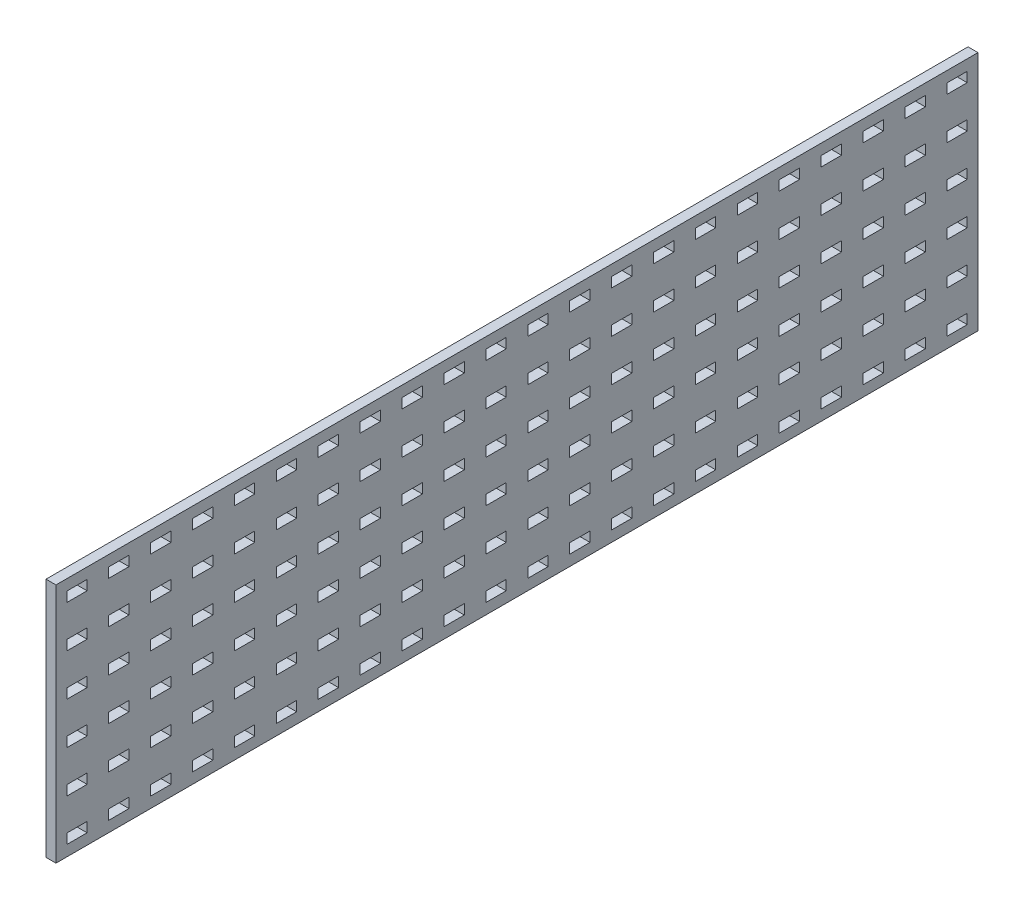
SolidWorks part; units mm, degrees
ref_plane "Front Plane" through (0, 0, 0) normal (0, 0, 1) x (1, 0, 0)
ref_plane "Top Plane" through (0, 0, 0) normal (0, 1, 0) x (1, 0, 0)
ref_plane "Right Plane" through (0, 0, 0) normal (1, 0, 0) x (0, 0, -1)
sketch "Sketch1" plane through (0, 0, 0) normal (1, 0, 0) x (0, 0, -1)
  line L1 (-279.4, -73.025) -> (279.4, -73.025)
  line L2 (-279.4, -73.025) -> (-279.4, 73.025)
  line L3 (-279.4, 73.025) -> (279.4, 73.025)
  line L4 (279.4, -73.025) -> (279.4, 73.025)
  line L5 (-279.4, -73.025) -> (279.4, 73.025) construction
  line L6 (-279.4, 73.025) -> (279.4, -73.025) construction
  point P0 (0, 0)
  dimension "D1" = 558.8
  dimension "D2" = 146.05
extrude "Boss-Extrude1" add sketch "Sketch1" along normal mid plane 6.0452
sketch "Sketch2" plane through (3.0226, 0, 0) normal (1, 0, 0) x (0, 0, -1)
  line L0 (-279.4, -73.025) -> (279.4, -73.025) construction
  line L1 (260.5405, -60.5) -> (272.8595, -60.5)
  line L2 (260.5405, -60.5) -> (260.5405, -66.5)
  line L3 (260.5405, -66.5) -> (272.8595, -66.5)
  line L4 (272.8595, -60.5) -> (272.8595, -66.5)
  line L5 (260.5405, -60.5) -> (272.8595, -66.5) construction
  line L6 (260.5405, -66.5) -> (272.8595, -60.5) construction
  line L7 (279.4, -73.025) -> (279.4, 73.025) construction
  line L8 (235.1405, -66.5) -> (247.4595, -66.5)
  line L9 (235.1405, -60.5) -> (235.1405, -66.5)
  line L10 (235.1405, -60.5) -> (247.4595, -60.5)
  line L11 (247.4595, -60.5) -> (247.4595, -66.5)
  line L12 (209.7405, -66.5) -> (222.0595, -66.5)
  line L13 (209.7405, -60.5) -> (209.7405, -66.5)
  line L14 (209.7405, -60.5) -> (222.0595, -60.5)
  line L15 (222.0595, -60.5) -> (222.0595, -66.5)
  line L16 (184.3405, -66.5) -> (196.6595, -66.5)
  line L17 (184.3405, -60.5) -> (184.3405, -66.5)
  line L18 (184.3405, -60.5) -> (196.6595, -60.5)
  line L19 (196.6595, -60.5) -> (196.6595, -66.5)
  line L20 (158.9405, -66.5) -> (171.2595, -66.5)
  line L21 (158.9405, -60.5) -> (158.9405, -66.5)
  line L22 (158.9405, -60.5) -> (171.2595, -60.5)
  line L23 (171.2595, -60.5) -> (171.2595, -66.5)
  line L24 (133.5405, -66.5) -> (145.8595, -66.5)
  line L25 (133.5405, -60.5) -> (133.5405, -66.5)
  line L26 (133.5405, -60.5) -> (145.8595, -60.5)
  line L27 (145.8595, -60.5) -> (145.8595, -66.5)
  line L28 (108.1405, -66.5) -> (120.4595, -66.5)
  line L29 (108.1405, -60.5) -> (108.1405, -66.5)
  line L30 (108.1405, -60.5) -> (120.4595, -60.5)
  line L31 (120.4595, -60.5) -> (120.4595, -66.5)
  line L32 (82.7405, -66.5) -> (95.0595, -66.5)
  line L33 (82.7405, -60.5) -> (82.7405, -66.5)
  line L34 (82.7405, -60.5) -> (95.0595, -60.5)
  line L35 (95.0595, -60.5) -> (95.0595, -66.5)
  line L36 (57.3405, -66.5) -> (69.6595, -66.5)
  line L37 (57.3405, -60.5) -> (57.3405, -66.5)
  line L38 (57.3405, -60.5) -> (69.6595, -60.5)
  line L39 (69.6595, -60.5) -> (69.6595, -66.5)
  line L40 (31.9405, -66.5) -> (44.2595, -66.5)
  line L41 (31.9405, -60.5) -> (31.9405, -66.5)
  line L42 (31.9405, -60.5) -> (44.2595, -60.5)
  line L43 (44.2595, -60.5) -> (44.2595, -66.5)
  line L44 (6.5405, -66.5) -> (18.8595, -66.5)
  line L45 (6.5405, -60.5) -> (6.5405, -66.5)
  line L46 (6.5405, -60.5) -> (18.8595, -60.5)
  line L47 (18.8595, -60.5) -> (18.8595, -66.5)
  line L48 (-18.8595, -66.5) -> (-6.5405, -66.5)
  line L49 (-18.8595, -60.5) -> (-18.8595, -66.5)
  line L50 (-18.8595, -60.5) -> (-6.5405, -60.5)
  line L51 (-6.5405, -60.5) -> (-6.5405, -66.5)
  line L52 (-44.2595, -66.5) -> (-31.9405, -66.5)
  line L53 (-44.2595, -60.5) -> (-44.2595, -66.5)
  line L54 (-44.2595, -60.5) -> (-31.9405, -60.5)
  line L55 (-31.9405, -60.5) -> (-31.9405, -66.5)
  line L56 (-69.6595, -66.5) -> (-57.3405, -66.5)
  line L57 (-69.6595, -60.5) -> (-69.6595, -66.5)
  line L58 (-69.6595, -60.5) -> (-57.3405, -60.5)
  line L59 (-57.3405, -60.5) -> (-57.3405, -66.5)
  line L60 (-95.0595, -66.5) -> (-82.7405, -66.5)
  line L61 (-95.0595, -60.5) -> (-95.0595, -66.5)
  line L62 (-95.0595, -60.5) -> (-82.7405, -60.5)
  line L63 (-82.7405, -60.5) -> (-82.7405, -66.5)
  line L64 (-120.4595, -66.5) -> (-108.1405, -66.5)
  line L65 (-120.4595, -60.5) -> (-120.4595, -66.5)
  line L66 (-120.4595, -60.5) -> (-108.1405, -60.5)
  line L67 (-108.1405, -60.5) -> (-108.1405, -66.5)
  line L68 (-145.8595, -66.5) -> (-133.5405, -66.5)
  line L69 (-145.8595, -60.5) -> (-145.8595, -66.5)
  line L70 (-145.8595, -60.5) -> (-133.5405, -60.5)
  line L71 (-133.5405, -60.5) -> (-133.5405, -66.5)
  line L72 (-171.2595, -66.5) -> (-158.9405, -66.5)
  line L73 (-171.2595, -60.5) -> (-171.2595, -66.5)
  line L74 (-171.2595, -60.5) -> (-158.9405, -60.5)
  line L75 (-158.9405, -60.5) -> (-158.9405, -66.5)
  line L76 (-196.6595, -66.5) -> (-184.3405, -66.5)
  line L77 (-196.6595, -60.5) -> (-196.6595, -66.5)
  line L78 (-196.6595, -60.5) -> (-184.3405, -60.5)
  line L79 (-184.3405, -60.5) -> (-184.3405, -66.5)
  line L80 (-222.0595, -66.5) -> (-209.7405, -66.5)
  line L81 (-222.0595, -60.5) -> (-222.0595, -66.5)
  line L82 (-222.0595, -60.5) -> (-209.7405, -60.5)
  line L83 (-209.7405, -60.5) -> (-209.7405, -66.5)
  line L84 (-247.4595, -66.5) -> (-235.1405, -66.5)
  line L85 (-247.4595, -60.5) -> (-247.4595, -66.5)
  line L86 (-247.4595, -60.5) -> (-235.1405, -60.5)
  line L87 (-235.1405, -60.5) -> (-235.1405, -66.5)
  line L88 (-272.8595, -66.5) -> (-260.5405, -66.5)
  line L89 (-272.8595, -60.5) -> (-272.8595, -66.5)
  line L90 (-272.8595, -60.5) -> (-260.5405, -60.5)
  line L91 (-260.5405, -60.5) -> (-260.5405, -66.5)
  line L92 (235.1405, -41.1) -> (247.4595, -41.1)
  line L93 (235.1405, -35.1) -> (235.1405, -41.1)
  line L94 (235.1405, -35.1) -> (247.4595, -35.1)
  line L95 (247.4595, -35.1) -> (247.4595, -41.1)
  line L96 (209.7405, -41.1) -> (222.0595, -41.1)
  line L97 (209.7405, -35.1) -> (209.7405, -41.1)
  line L98 (209.7405, -35.1) -> (222.0595, -35.1)
  line L99 (222.0595, -35.1) -> (222.0595, -41.1)
  line L100 (184.3405, -41.1) -> (196.6595, -41.1)
  line L101 (184.3405, -35.1) -> (184.3405, -41.1)
  line L102 (184.3405, -35.1) -> (196.6595, -35.1)
  line L103 (196.6595, -35.1) -> (196.6595, -41.1)
  line L104 (158.9405, -41.1) -> (171.2595, -41.1)
  line L105 (158.9405, -35.1) -> (158.9405, -41.1)
  line L106 (158.9405, -35.1) -> (171.2595, -35.1)
  line L107 (171.2595, -35.1) -> (171.2595, -41.1)
  line L108 (133.5405, -41.1) -> (145.8595, -41.1)
  line L109 (133.5405, -35.1) -> (133.5405, -41.1)
  line L110 (133.5405, -35.1) -> (145.8595, -35.1)
  line L111 (145.8595, -35.1) -> (145.8595, -41.1)
  line L112 (108.1405, -41.1) -> (120.4595, -41.1)
  line L113 (108.1405, -35.1) -> (108.1405, -41.1)
  line L114 (108.1405, -35.1) -> (120.4595, -35.1)
  line L115 (120.4595, -35.1) -> (120.4595, -41.1)
  line L116 (82.7405, -41.1) -> (95.0595, -41.1)
  line L117 (82.7405, -35.1) -> (82.7405, -41.1)
  line L118 (82.7405, -35.1) -> (95.0595, -35.1)
  line L119 (95.0595, -35.1) -> (95.0595, -41.1)
  line L120 (57.3405, -41.1) -> (69.6595, -41.1)
  line L121 (57.3405, -35.1) -> (57.3405, -41.1)
  line L122 (57.3405, -35.1) -> (69.6595, -35.1)
  line L123 (69.6595, -35.1) -> (69.6595, -41.1)
  line L124 (31.9405, -41.1) -> (44.2595, -41.1)
  line L125 (31.9405, -35.1) -> (31.9405, -41.1)
  line L126 (31.9405, -35.1) -> (44.2595, -35.1)
  line L127 (44.2595, -35.1) -> (44.2595, -41.1)
  line L128 (6.5405, -41.1) -> (18.8595, -41.1)
  line L129 (6.5405, -35.1) -> (6.5405, -41.1)
  line L130 (6.5405, -35.1) -> (18.8595, -35.1)
  line L131 (18.8595, -35.1) -> (18.8595, -41.1)
  line L132 (-18.8595, -41.1) -> (-6.5405, -41.1)
  line L133 (-18.8595, -35.1) -> (-18.8595, -41.1)
  line L134 (-18.8595, -35.1) -> (-6.5405, -35.1)
  line L135 (-6.5405, -35.1) -> (-6.5405, -41.1)
  line L136 (-44.2595, -41.1) -> (-31.9405, -41.1)
  line L137 (-44.2595, -35.1) -> (-44.2595, -41.1)
  line L138 (-44.2595, -35.1) -> (-31.9405, -35.1)
  line L139 (-31.9405, -35.1) -> (-31.9405, -41.1)
  line L140 (-69.6595, -41.1) -> (-57.3405, -41.1)
  line L141 (-69.6595, -35.1) -> (-69.6595, -41.1)
  line L142 (-69.6595, -35.1) -> (-57.3405, -35.1)
  line L143 (-57.3405, -35.1) -> (-57.3405, -41.1)
  line L144 (-95.0595, -41.1) -> (-82.7405, -41.1)
  line L145 (-95.0595, -35.1) -> (-95.0595, -41.1)
  line L146 (-95.0595, -35.1) -> (-82.7405, -35.1)
  line L147 (-82.7405, -35.1) -> (-82.7405, -41.1)
  line L148 (-120.4595, -41.1) -> (-108.1405, -41.1)
  line L149 (-120.4595, -35.1) -> (-120.4595, -41.1)
  line L150 (-120.4595, -35.1) -> (-108.1405, -35.1)
  line L151 (-108.1405, -35.1) -> (-108.1405, -41.1)
  line L152 (-145.8595, -41.1) -> (-133.5405, -41.1)
  line L153 (-145.8595, -35.1) -> (-145.8595, -41.1)
  line L154 (-145.8595, -35.1) -> (-133.5405, -35.1)
  line L155 (-133.5405, -35.1) -> (-133.5405, -41.1)
  line L156 (-171.2595, -41.1) -> (-158.9405, -41.1)
  line L157 (-171.2595, -35.1) -> (-171.2595, -41.1)
  line L158 (-171.2595, -35.1) -> (-158.9405, -35.1)
  line L159 (-158.9405, -35.1) -> (-158.9405, -41.1)
  line L160 (-196.6595, -41.1) -> (-184.3405, -41.1)
  line L161 (-196.6595, -35.1) -> (-196.6595, -41.1)
  line L162 (-196.6595, -35.1) -> (-184.3405, -35.1)
  line L163 (-184.3405, -35.1) -> (-184.3405, -41.1)
  line L164 (-222.0595, -41.1) -> (-209.7405, -41.1)
  line L165 (-222.0595, -35.1) -> (-222.0595, -41.1)
  line L166 (-222.0595, -35.1) -> (-209.7405, -35.1)
  line L167 (-209.7405, -35.1) -> (-209.7405, -41.1)
  line L168 (-247.4595, -41.1) -> (-235.1405, -41.1)
  line L169 (-247.4595, -35.1) -> (-247.4595, -41.1)
  line L170 (-247.4595, -35.1) -> (-235.1405, -35.1)
  line L171 (-235.1405, -35.1) -> (-235.1405, -41.1)
  line L172 (-272.8595, -41.1) -> (-260.5405, -41.1)
  line L173 (-272.8595, -35.1) -> (-272.8595, -41.1)
  line L174 (-272.8595, -35.1) -> (-260.5405, -35.1)
  line L175 (-260.5405, -35.1) -> (-260.5405, -41.1)
  line L176 (235.1405, -15.7) -> (247.4595, -15.7)
  line L177 (235.1405, -9.7) -> (235.1405, -15.7)
  line L178 (235.1405, -9.7) -> (247.4595, -9.7)
  line L179 (247.4595, -9.7) -> (247.4595, -15.7)
  line L180 (209.7405, -15.7) -> (222.0595, -15.7)
  line L181 (209.7405, -9.7) -> (209.7405, -15.7)
  line L182 (209.7405, -9.7) -> (222.0595, -9.7)
  line L183 (222.0595, -9.7) -> (222.0595, -15.7)
  line L184 (184.3405, -15.7) -> (196.6595, -15.7)
  line L185 (184.3405, -9.7) -> (184.3405, -15.7)
  line L186 (184.3405, -9.7) -> (196.6595, -9.7)
  line L187 (196.6595, -9.7) -> (196.6595, -15.7)
  line L188 (158.9405, -15.7) -> (171.2595, -15.7)
  line L189 (158.9405, -9.7) -> (158.9405, -15.7)
  line L190 (158.9405, -9.7) -> (171.2595, -9.7)
  line L191 (171.2595, -9.7) -> (171.2595, -15.7)
  line L192 (133.5405, -15.7) -> (145.8595, -15.7)
  line L193 (133.5405, -9.7) -> (133.5405, -15.7)
  line L194 (133.5405, -9.7) -> (145.8595, -9.7)
  line L195 (145.8595, -9.7) -> (145.8595, -15.7)
  line L196 (108.1405, -15.7) -> (120.4595, -15.7)
  line L197 (108.1405, -9.7) -> (108.1405, -15.7)
  line L198 (108.1405, -9.7) -> (120.4595, -9.7)
  line L199 (120.4595, -9.7) -> (120.4595, -15.7)
  line L200 (82.7405, -15.7) -> (95.0595, -15.7)
  line L201 (82.7405, -9.7) -> (82.7405, -15.7)
  line L202 (82.7405, -9.7) -> (95.0595, -9.7)
  line L203 (95.0595, -9.7) -> (95.0595, -15.7)
  line L204 (57.3405, -15.7) -> (69.6595, -15.7)
  line L205 (57.3405, -9.7) -> (57.3405, -15.7)
  line L206 (57.3405, -9.7) -> (69.6595, -9.7)
  line L207 (69.6595, -9.7) -> (69.6595, -15.7)
  line L208 (31.9405, -15.7) -> (44.2595, -15.7)
  line L209 (31.9405, -9.7) -> (31.9405, -15.7)
  line L210 (31.9405, -9.7) -> (44.2595, -9.7)
  line L211 (44.2595, -9.7) -> (44.2595, -15.7)
  line L212 (6.5405, -15.7) -> (18.8595, -15.7)
  line L213 (6.5405, -9.7) -> (6.5405, -15.7)
  line L214 (6.5405, -9.7) -> (18.8595, -9.7)
  line L215 (18.8595, -9.7) -> (18.8595, -15.7)
  line L216 (-18.8595, -15.7) -> (-6.5405, -15.7)
  line L217 (-18.8595, -9.7) -> (-18.8595, -15.7)
  line L218 (-18.8595, -9.7) -> (-6.5405, -9.7)
  line L219 (-6.5405, -9.7) -> (-6.5405, -15.7)
  line L220 (-44.2595, -15.7) -> (-31.9405, -15.7)
  line L221 (-44.2595, -9.7) -> (-44.2595, -15.7)
  line L222 (-44.2595, -9.7) -> (-31.9405, -9.7)
  line L223 (-31.9405, -9.7) -> (-31.9405, -15.7)
  line L224 (-69.6595, -15.7) -> (-57.3405, -15.7)
  line L225 (-69.6595, -9.7) -> (-69.6595, -15.7)
  line L226 (-69.6595, -9.7) -> (-57.3405, -9.7)
  line L227 (-57.3405, -9.7) -> (-57.3405, -15.7)
  line L228 (-95.0595, -15.7) -> (-82.7405, -15.7)
  line L229 (-95.0595, -9.7) -> (-95.0595, -15.7)
  line L230 (-95.0595, -9.7) -> (-82.7405, -9.7)
  line L231 (-82.7405, -9.7) -> (-82.7405, -15.7)
  line L232 (-120.4595, -15.7) -> (-108.1405, -15.7)
  line L233 (-120.4595, -9.7) -> (-120.4595, -15.7)
  line L234 (-120.4595, -9.7) -> (-108.1405, -9.7)
  line L235 (-108.1405, -9.7) -> (-108.1405, -15.7)
  line L236 (-145.8595, -15.7) -> (-133.5405, -15.7)
  line L237 (-145.8595, -9.7) -> (-145.8595, -15.7)
  line L238 (-145.8595, -9.7) -> (-133.5405, -9.7)
  line L239 (-133.5405, -9.7) -> (-133.5405, -15.7)
  line L240 (-171.2595, -15.7) -> (-158.9405, -15.7)
  line L241 (-171.2595, -9.7) -> (-171.2595, -15.7)
  line L242 (-171.2595, -9.7) -> (-158.9405, -9.7)
  line L243 (-158.9405, -9.7) -> (-158.9405, -15.7)
  line L244 (-196.6595, -15.7) -> (-184.3405, -15.7)
  line L245 (-196.6595, -9.7) -> (-196.6595, -15.7)
  line L246 (-196.6595, -9.7) -> (-184.3405, -9.7)
  line L247 (-184.3405, -9.7) -> (-184.3405, -15.7)
  line L248 (-222.0595, -15.7) -> (-209.7405, -15.7)
  line L249 (-222.0595, -9.7) -> (-222.0595, -15.7)
  line L250 (-222.0595, -9.7) -> (-209.7405, -9.7)
  line L251 (-209.7405, -9.7) -> (-209.7405, -15.7)
  line L252 (-247.4595, -15.7) -> (-235.1405, -15.7)
  line L253 (-247.4595, -9.7) -> (-247.4595, -15.7)
  line L254 (-247.4595, -9.7) -> (-235.1405, -9.7)
  line L255 (-235.1405, -9.7) -> (-235.1405, -15.7)
  line L256 (-272.8595, -15.7) -> (-260.5405, -15.7)
  line L257 (-272.8595, -9.7) -> (-272.8595, -15.7)
  line L258 (-272.8595, -9.7) -> (-260.5405, -9.7)
  line L259 (-260.5405, -9.7) -> (-260.5405, -15.7)
  line L260 (235.1405, 9.7) -> (247.4595, 9.7)
  line L261 (235.1405, 15.7) -> (235.1405, 9.7)
  line L262 (235.1405, 15.7) -> (247.4595, 15.7)
  line L263 (247.4595, 15.7) -> (247.4595, 9.7)
  line L264 (209.7405, 9.7) -> (222.0595, 9.7)
  line L265 (209.7405, 15.7) -> (209.7405, 9.7)
  line L266 (209.7405, 15.7) -> (222.0595, 15.7)
  line L267 (222.0595, 15.7) -> (222.0595, 9.7)
  line L268 (184.3405, 9.7) -> (196.6595, 9.7)
  line L269 (184.3405, 15.7) -> (184.3405, 9.7)
  line L270 (184.3405, 15.7) -> (196.6595, 15.7)
  line L271 (196.6595, 15.7) -> (196.6595, 9.7)
  line L272 (158.9405, 9.7) -> (171.2595, 9.7)
  line L273 (158.9405, 15.7) -> (158.9405, 9.7)
  line L274 (158.9405, 15.7) -> (171.2595, 15.7)
  line L275 (171.2595, 15.7) -> (171.2595, 9.7)
  line L276 (133.5405, 9.7) -> (145.8595, 9.7)
  line L277 (133.5405, 15.7) -> (133.5405, 9.7)
  line L278 (133.5405, 15.7) -> (145.8595, 15.7)
  line L279 (145.8595, 15.7) -> (145.8595, 9.7)
  line L280 (108.1405, 9.7) -> (120.4595, 9.7)
  line L281 (108.1405, 15.7) -> (108.1405, 9.7)
  line L282 (108.1405, 15.7) -> (120.4595, 15.7)
  line L283 (120.4595, 15.7) -> (120.4595, 9.7)
  line L284 (82.7405, 9.7) -> (95.0595, 9.7)
  line L285 (82.7405, 15.7) -> (82.7405, 9.7)
  line L286 (82.7405, 15.7) -> (95.0595, 15.7)
  line L287 (95.0595, 15.7) -> (95.0595, 9.7)
  line L288 (57.3405, 9.7) -> (69.6595, 9.7)
  line L289 (57.3405, 15.7) -> (57.3405, 9.7)
  line L290 (57.3405, 15.7) -> (69.6595, 15.7)
  line L291 (69.6595, 15.7) -> (69.6595, 9.7)
  line L292 (31.9405, 9.7) -> (44.2595, 9.7)
  line L293 (31.9405, 15.7) -> (31.9405, 9.7)
  line L294 (31.9405, 15.7) -> (44.2595, 15.7)
  line L295 (44.2595, 15.7) -> (44.2595, 9.7)
  line L296 (6.5405, 9.7) -> (18.8595, 9.7)
  line L297 (6.5405, 15.7) -> (6.5405, 9.7)
  line L298 (6.5405, 15.7) -> (18.8595, 15.7)
  line L299 (18.8595, 15.7) -> (18.8595, 9.7)
  line L300 (-18.8595, 9.7) -> (-6.5405, 9.7)
  line L301 (-18.8595, 15.7) -> (-18.8595, 9.7)
  line L302 (-18.8595, 15.7) -> (-6.5405, 15.7)
  line L303 (-6.5405, 15.7) -> (-6.5405, 9.7)
  line L304 (-44.2595, 9.7) -> (-31.9405, 9.7)
  line L305 (-44.2595, 15.7) -> (-44.2595, 9.7)
  line L306 (-44.2595, 15.7) -> (-31.9405, 15.7)
  line L307 (-31.9405, 15.7) -> (-31.9405, 9.7)
  line L308 (-69.6595, 9.7) -> (-57.3405, 9.7)
  line L309 (-69.6595, 15.7) -> (-69.6595, 9.7)
  line L310 (-69.6595, 15.7) -> (-57.3405, 15.7)
  line L311 (-57.3405, 15.7) -> (-57.3405, 9.7)
  line L312 (-95.0595, 9.7) -> (-82.7405, 9.7)
  line L313 (-95.0595, 15.7) -> (-95.0595, 9.7)
  line L314 (-95.0595, 15.7) -> (-82.7405, 15.7)
  line L315 (-82.7405, 15.7) -> (-82.7405, 9.7)
  line L316 (-120.4595, 9.7) -> (-108.1405, 9.7)
  line L317 (-120.4595, 15.7) -> (-120.4595, 9.7)
  line L318 (-120.4595, 15.7) -> (-108.1405, 15.7)
  line L319 (-108.1405, 15.7) -> (-108.1405, 9.7)
  line L320 (-145.8595, 9.7) -> (-133.5405, 9.7)
  line L321 (-145.8595, 15.7) -> (-145.8595, 9.7)
  line L322 (-145.8595, 15.7) -> (-133.5405, 15.7)
  line L323 (-133.5405, 15.7) -> (-133.5405, 9.7)
  line L324 (-171.2595, 9.7) -> (-158.9405, 9.7)
  line L325 (-171.2595, 15.7) -> (-171.2595, 9.7)
  line L326 (-171.2595, 15.7) -> (-158.9405, 15.7)
  line L327 (-158.9405, 15.7) -> (-158.9405, 9.7)
  line L328 (-196.6595, 9.7) -> (-184.3405, 9.7)
  line L329 (-196.6595, 15.7) -> (-196.6595, 9.7)
  line L330 (-196.6595, 15.7) -> (-184.3405, 15.7)
  line L331 (-184.3405, 15.7) -> (-184.3405, 9.7)
  line L332 (-222.0595, 9.7) -> (-209.7405, 9.7)
  line L333 (-222.0595, 15.7) -> (-222.0595, 9.7)
  line L334 (-222.0595, 15.7) -> (-209.7405, 15.7)
  line L335 (-209.7405, 15.7) -> (-209.7405, 9.7)
  line L336 (-247.4595, 9.7) -> (-235.1405, 9.7)
  line L337 (-247.4595, 15.7) -> (-247.4595, 9.7)
  line L338 (-247.4595, 15.7) -> (-235.1405, 15.7)
  line L339 (-235.1405, 15.7) -> (-235.1405, 9.7)
  line L340 (-272.8595, 9.7) -> (-260.5405, 9.7)
  line L341 (-272.8595, 15.7) -> (-272.8595, 9.7)
  line L342 (-272.8595, 15.7) -> (-260.5405, 15.7)
  line L343 (-260.5405, 15.7) -> (-260.5405, 9.7)
  line L344 (235.1405, 35.1) -> (247.4595, 35.1)
  line L345 (235.1405, 41.1) -> (235.1405, 35.1)
  line L346 (235.1405, 41.1) -> (247.4595, 41.1)
  line L347 (247.4595, 41.1) -> (247.4595, 35.1)
  line L348 (209.7405, 35.1) -> (222.0595, 35.1)
  line L349 (209.7405, 41.1) -> (209.7405, 35.1)
  line L350 (209.7405, 41.1) -> (222.0595, 41.1)
  line L351 (222.0595, 41.1) -> (222.0595, 35.1)
  line L352 (184.3405, 35.1) -> (196.6595, 35.1)
  line L353 (184.3405, 41.1) -> (184.3405, 35.1)
  line L354 (184.3405, 41.1) -> (196.6595, 41.1)
  line L355 (196.6595, 41.1) -> (196.6595, 35.1)
  line L356 (158.9405, 35.1) -> (171.2595, 35.1)
  line L357 (158.9405, 41.1) -> (158.9405, 35.1)
  line L358 (158.9405, 41.1) -> (171.2595, 41.1)
  line L359 (171.2595, 41.1) -> (171.2595, 35.1)
  line L360 (133.5405, 35.1) -> (145.8595, 35.1)
  line L361 (133.5405, 41.1) -> (133.5405, 35.1)
  line L362 (133.5405, 41.1) -> (145.8595, 41.1)
  line L363 (145.8595, 41.1) -> (145.8595, 35.1)
  line L364 (108.1405, 35.1) -> (120.4595, 35.1)
  line L365 (108.1405, 41.1) -> (108.1405, 35.1)
  line L366 (108.1405, 41.1) -> (120.4595, 41.1)
  line L367 (120.4595, 41.1) -> (120.4595, 35.1)
  line L368 (82.7405, 35.1) -> (95.0595, 35.1)
  line L369 (82.7405, 41.1) -> (82.7405, 35.1)
  line L370 (82.7405, 41.1) -> (95.0595, 41.1)
  line L371 (95.0595, 41.1) -> (95.0595, 35.1)
  line L372 (57.3405, 35.1) -> (69.6595, 35.1)
  line L373 (57.3405, 41.1) -> (57.3405, 35.1)
  line L374 (57.3405, 41.1) -> (69.6595, 41.1)
  line L375 (69.6595, 41.1) -> (69.6595, 35.1)
  line L376 (31.9405, 35.1) -> (44.2595, 35.1)
  line L377 (31.9405, 41.1) -> (31.9405, 35.1)
  line L378 (31.9405, 41.1) -> (44.2595, 41.1)
  line L379 (44.2595, 41.1) -> (44.2595, 35.1)
  line L380 (6.5405, 35.1) -> (18.8595, 35.1)
  line L381 (6.5405, 41.1) -> (6.5405, 35.1)
  line L382 (6.5405, 41.1) -> (18.8595, 41.1)
  line L383 (18.8595, 41.1) -> (18.8595, 35.1)
  line L384 (-18.8595, 35.1) -> (-6.5405, 35.1)
  line L385 (-18.8595, 41.1) -> (-18.8595, 35.1)
  line L386 (-18.8595, 41.1) -> (-6.5405, 41.1)
  line L387 (-6.5405, 41.1) -> (-6.5405, 35.1)
  line L388 (-44.2595, 35.1) -> (-31.9405, 35.1)
  line L389 (-44.2595, 41.1) -> (-44.2595, 35.1)
  line L390 (-44.2595, 41.1) -> (-31.9405, 41.1)
  line L391 (-31.9405, 41.1) -> (-31.9405, 35.1)
  line L392 (-69.6595, 35.1) -> (-57.3405, 35.1)
  line L393 (-69.6595, 41.1) -> (-69.6595, 35.1)
  line L394 (-69.6595, 41.1) -> (-57.3405, 41.1)
  line L395 (-57.3405, 41.1) -> (-57.3405, 35.1)
  line L396 (-95.0595, 35.1) -> (-82.7405, 35.1)
  line L397 (-95.0595, 41.1) -> (-95.0595, 35.1)
  line L398 (-95.0595, 41.1) -> (-82.7405, 41.1)
  line L399 (-82.7405, 41.1) -> (-82.7405, 35.1)
  line L400 (-120.4595, 35.1) -> (-108.1405, 35.1)
  line L401 (-120.4595, 41.1) -> (-120.4595, 35.1)
  line L402 (-120.4595, 41.1) -> (-108.1405, 41.1)
  line L403 (-108.1405, 41.1) -> (-108.1405, 35.1)
  line L404 (-145.8595, 35.1) -> (-133.5405, 35.1)
  line L405 (-145.8595, 41.1) -> (-145.8595, 35.1)
  line L406 (-145.8595, 41.1) -> (-133.5405, 41.1)
  line L407 (-133.5405, 41.1) -> (-133.5405, 35.1)
  line L408 (-171.2595, 35.1) -> (-158.9405, 35.1)
  line L409 (-171.2595, 41.1) -> (-171.2595, 35.1)
  line L410 (-171.2595, 41.1) -> (-158.9405, 41.1)
  line L411 (-158.9405, 41.1) -> (-158.9405, 35.1)
  line L412 (-196.6595, 35.1) -> (-184.3405, 35.1)
  line L413 (-196.6595, 41.1) -> (-196.6595, 35.1)
  line L414 (-196.6595, 41.1) -> (-184.3405, 41.1)
  line L415 (-184.3405, 41.1) -> (-184.3405, 35.1)
  line L416 (-222.0595, 35.1) -> (-209.7405, 35.1)
  line L417 (-222.0595, 41.1) -> (-222.0595, 35.1)
  line L418 (-222.0595, 41.1) -> (-209.7405, 41.1)
  line L419 (-209.7405, 41.1) -> (-209.7405, 35.1)
  line L420 (-247.4595, 35.1) -> (-235.1405, 35.1)
  line L421 (-247.4595, 41.1) -> (-247.4595, 35.1)
  line L422 (-247.4595, 41.1) -> (-235.1405, 41.1)
  line L423 (-235.1405, 41.1) -> (-235.1405, 35.1)
  line L424 (-272.8595, 35.1) -> (-260.5405, 35.1)
  line L425 (-272.8595, 41.1) -> (-272.8595, 35.1)
  line L426 (-272.8595, 41.1) -> (-260.5405, 41.1)
  line L427 (-260.5405, 41.1) -> (-260.5405, 35.1)
  line L428 (235.1405, 60.5) -> (247.4595, 60.5)
  line L429 (235.1405, 66.5) -> (235.1405, 60.5)
  line L430 (235.1405, 66.5) -> (247.4595, 66.5)
  line L431 (247.4595, 66.5) -> (247.4595, 60.5)
  line L432 (209.7405, 60.5) -> (222.0595, 60.5)
  line L433 (209.7405, 66.5) -> (209.7405, 60.5)
  line L434 (209.7405, 66.5) -> (222.0595, 66.5)
  line L435 (222.0595, 66.5) -> (222.0595, 60.5)
  line L436 (184.3405, 60.5) -> (196.6595, 60.5)
  line L437 (184.3405, 66.5) -> (184.3405, 60.5)
  line L438 (184.3405, 66.5) -> (196.6595, 66.5)
  line L439 (196.6595, 66.5) -> (196.6595, 60.5)
  line L440 (158.9405, 60.5) -> (171.2595, 60.5)
  line L441 (158.9405, 66.5) -> (158.9405, 60.5)
  line L442 (158.9405, 66.5) -> (171.2595, 66.5)
  line L443 (171.2595, 66.5) -> (171.2595, 60.5)
  line L444 (133.5405, 60.5) -> (145.8595, 60.5)
  line L445 (133.5405, 66.5) -> (133.5405, 60.5)
  line L446 (133.5405, 66.5) -> (145.8595, 66.5)
  line L447 (145.8595, 66.5) -> (145.8595, 60.5)
  line L448 (108.1405, 60.5) -> (120.4595, 60.5)
  line L449 (108.1405, 66.5) -> (108.1405, 60.5)
  line L450 (108.1405, 66.5) -> (120.4595, 66.5)
  line L451 (120.4595, 66.5) -> (120.4595, 60.5)
  line L452 (82.7405, 60.5) -> (95.0595, 60.5)
  line L453 (82.7405, 66.5) -> (82.7405, 60.5)
  line L454 (82.7405, 66.5) -> (95.0595, 66.5)
  line L455 (95.0595, 66.5) -> (95.0595, 60.5)
  line L456 (57.3405, 60.5) -> (69.6595, 60.5)
  line L457 (57.3405, 66.5) -> (57.3405, 60.5)
  line L458 (57.3405, 66.5) -> (69.6595, 66.5)
  line L459 (69.6595, 66.5) -> (69.6595, 60.5)
  line L460 (31.9405, 60.5) -> (44.2595, 60.5)
  line L461 (31.9405, 66.5) -> (31.9405, 60.5)
  line L462 (31.9405, 66.5) -> (44.2595, 66.5)
  line L463 (44.2595, 66.5) -> (44.2595, 60.5)
  line L464 (6.5405, 60.5) -> (18.8595, 60.5)
  line L465 (6.5405, 66.5) -> (6.5405, 60.5)
  line L466 (6.5405, 66.5) -> (18.8595, 66.5)
  line L467 (18.8595, 66.5) -> (18.8595, 60.5)
  line L468 (-18.8595, 60.5) -> (-6.5405, 60.5)
  line L469 (-18.8595, 66.5) -> (-18.8595, 60.5)
  line L470 (-18.8595, 66.5) -> (-6.5405, 66.5)
  line L471 (-6.5405, 66.5) -> (-6.5405, 60.5)
  line L472 (-44.2595, 60.5) -> (-31.9405, 60.5)
  line L473 (-44.2595, 66.5) -> (-44.2595, 60.5)
  line L474 (-44.2595, 66.5) -> (-31.9405, 66.5)
  line L475 (-31.9405, 66.5) -> (-31.9405, 60.5)
  line L476 (-69.6595, 60.5) -> (-57.3405, 60.5)
  line L477 (-69.6595, 66.5) -> (-69.6595, 60.5)
  line L478 (-69.6595, 66.5) -> (-57.3405, 66.5)
  line L479 (-57.3405, 66.5) -> (-57.3405, 60.5)
  line L480 (-95.0595, 60.5) -> (-82.7405, 60.5)
  line L481 (-95.0595, 66.5) -> (-95.0595, 60.5)
  line L482 (-95.0595, 66.5) -> (-82.7405, 66.5)
  line L483 (-82.7405, 66.5) -> (-82.7405, 60.5)
  line L484 (-120.4595, 60.5) -> (-108.1405, 60.5)
  line L485 (-120.4595, 66.5) -> (-120.4595, 60.5)
  line L486 (-120.4595, 66.5) -> (-108.1405, 66.5)
  line L487 (-108.1405, 66.5) -> (-108.1405, 60.5)
  line L488 (-145.8595, 60.5) -> (-133.5405, 60.5)
  line L489 (-145.8595, 66.5) -> (-145.8595, 60.5)
  line L490 (-145.8595, 66.5) -> (-133.5405, 66.5)
  line L491 (-133.5405, 66.5) -> (-133.5405, 60.5)
  line L492 (-171.2595, 60.5) -> (-158.9405, 60.5)
  line L493 (-171.2595, 66.5) -> (-171.2595, 60.5)
  line L494 (-171.2595, 66.5) -> (-158.9405, 66.5)
  line L495 (-158.9405, 66.5) -> (-158.9405, 60.5)
  line L496 (-196.6595, 60.5) -> (-184.3405, 60.5)
  line L497 (-196.6595, 66.5) -> (-196.6595, 60.5)
  line L498 (-196.6595, 66.5) -> (-184.3405, 66.5)
  line L499 (-184.3405, 66.5) -> (-184.3405, 60.5)
  line L500 (-222.0595, 60.5) -> (-209.7405, 60.5)
  line L501 (-222.0595, 66.5) -> (-222.0595, 60.5)
  line L502 (-222.0595, 66.5) -> (-209.7405, 66.5)
  line L503 (-209.7405, 66.5) -> (-209.7405, 60.5)
  line L504 (-247.4595, 60.5) -> (-235.1405, 60.5)
  line L505 (-247.4595, 66.5) -> (-247.4595, 60.5)
  line L506 (-247.4595, 66.5) -> (-235.1405, 66.5)
  line L507 (-235.1405, 66.5) -> (-235.1405, 60.5)
  line L508 (-272.8595, 60.5) -> (-260.5405, 60.5)
  line L509 (-272.8595, 66.5) -> (-272.8595, 60.5)
  line L510 (-272.8595, 66.5) -> (-260.5405, 66.5)
  line L511 (-260.5405, 66.5) -> (-260.5405, 60.5)
  line L512 (235.1405, 85.9) -> (247.4595, 85.9)
  line L513 (235.1405, 91.9) -> (235.1405, 85.9)
  line L514 (235.1405, 91.9) -> (247.4595, 91.9)
  line L515 (247.4595, 91.9) -> (247.4595, 85.9)
  line L516 (209.7405, 85.9) -> (222.0595, 85.9)
  line L517 (209.7405, 91.9) -> (209.7405, 85.9)
  line L518 (209.7405, 91.9) -> (222.0595, 91.9)
  line L519 (222.0595, 91.9) -> (222.0595, 85.9)
  line L520 (184.3405, 85.9) -> (196.6595, 85.9)
  line L521 (184.3405, 91.9) -> (184.3405, 85.9)
  line L522 (184.3405, 91.9) -> (196.6595, 91.9)
  line L523 (196.6595, 91.9) -> (196.6595, 85.9)
  line L524 (158.9405, 85.9) -> (171.2595, 85.9)
  line L525 (158.9405, 91.9) -> (158.9405, 85.9)
  line L526 (158.9405, 91.9) -> (171.2595, 91.9)
  line L527 (171.2595, 91.9) -> (171.2595, 85.9)
  line L528 (133.5405, 85.9) -> (145.8595, 85.9)
  line L529 (133.5405, 91.9) -> (133.5405, 85.9)
  line L530 (133.5405, 91.9) -> (145.8595, 91.9)
  line L531 (145.8595, 91.9) -> (145.8595, 85.9)
  line L532 (108.1405, 85.9) -> (120.4595, 85.9)
  line L533 (108.1405, 91.9) -> (108.1405, 85.9)
  line L534 (108.1405, 91.9) -> (120.4595, 91.9)
  line L535 (120.4595, 91.9) -> (120.4595, 85.9)
  line L536 (82.7405, 85.9) -> (95.0595, 85.9)
  line L537 (82.7405, 91.9) -> (82.7405, 85.9)
  line L538 (82.7405, 91.9) -> (95.0595, 91.9)
  line L539 (95.0595, 91.9) -> (95.0595, 85.9)
  line L540 (57.3405, 85.9) -> (69.6595, 85.9)
  line L541 (57.3405, 91.9) -> (57.3405, 85.9)
  line L542 (57.3405, 91.9) -> (69.6595, 91.9)
  line L543 (69.6595, 91.9) -> (69.6595, 85.9)
  line L544 (31.9405, 85.9) -> (44.2595, 85.9)
  line L545 (31.9405, 91.9) -> (31.9405, 85.9)
  line L546 (31.9405, 91.9) -> (44.2595, 91.9)
  line L547 (44.2595, 91.9) -> (44.2595, 85.9)
  line L548 (6.5405, 85.9) -> (18.8595, 85.9)
  line L549 (6.5405, 91.9) -> (6.5405, 85.9)
  line L550 (6.5405, 91.9) -> (18.8595, 91.9)
  line L551 (18.8595, 91.9) -> (18.8595, 85.9)
  line L552 (-18.8595, 85.9) -> (-6.5405, 85.9)
  line L553 (-18.8595, 91.9) -> (-18.8595, 85.9)
  line L554 (-18.8595, 91.9) -> (-6.5405, 91.9)
  line L555 (-6.5405, 91.9) -> (-6.5405, 85.9)
  line L556 (-44.2595, 85.9) -> (-31.9405, 85.9)
  line L557 (-44.2595, 91.9) -> (-44.2595, 85.9)
  line L558 (-44.2595, 91.9) -> (-31.9405, 91.9)
  line L559 (-31.9405, 91.9) -> (-31.9405, 85.9)
  line L560 (-69.6595, 85.9) -> (-57.3405, 85.9)
  line L561 (-69.6595, 91.9) -> (-69.6595, 85.9)
  line L562 (-69.6595, 91.9) -> (-57.3405, 91.9)
  line L563 (-57.3405, 91.9) -> (-57.3405, 85.9)
  line L564 (-95.0595, 85.9) -> (-82.7405, 85.9)
  line L565 (-95.0595, 91.9) -> (-95.0595, 85.9)
  line L566 (-95.0595, 91.9) -> (-82.7405, 91.9)
  line L567 (-82.7405, 91.9) -> (-82.7405, 85.9)
  line L568 (-120.4595, 85.9) -> (-108.1405, 85.9)
  line L569 (-120.4595, 91.9) -> (-120.4595, 85.9)
  line L570 (-120.4595, 91.9) -> (-108.1405, 91.9)
  line L571 (-108.1405, 91.9) -> (-108.1405, 85.9)
  line L572 (-145.8595, 85.9) -> (-133.5405, 85.9)
  line L573 (-145.8595, 91.9) -> (-145.8595, 85.9)
  line L574 (-145.8595, 91.9) -> (-133.5405, 91.9)
  line L575 (-133.5405, 91.9) -> (-133.5405, 85.9)
  line L576 (-171.2595, 85.9) -> (-158.9405, 85.9)
  line L577 (-171.2595, 91.9) -> (-171.2595, 85.9)
  line L578 (-171.2595, 91.9) -> (-158.9405, 91.9)
  line L579 (-158.9405, 91.9) -> (-158.9405, 85.9)
  line L580 (-196.6595, 85.9) -> (-184.3405, 85.9)
  line L581 (-196.6595, 91.9) -> (-196.6595, 85.9)
  line L582 (-196.6595, 91.9) -> (-184.3405, 91.9)
  line L583 (-184.3405, 91.9) -> (-184.3405, 85.9)
  line L584 (-222.0595, 85.9) -> (-209.7405, 85.9)
  line L585 (-222.0595, 91.9) -> (-222.0595, 85.9)
  line L586 (-222.0595, 91.9) -> (-209.7405, 91.9)
  line L587 (-209.7405, 91.9) -> (-209.7405, 85.9)
  line L588 (-247.4595, 85.9) -> (-235.1405, 85.9)
  line L589 (-247.4595, 91.9) -> (-247.4595, 85.9)
  line L590 (-247.4595, 91.9) -> (-235.1405, 91.9)
  line L591 (-235.1405, 91.9) -> (-235.1405, 85.9)
  line L592 (-272.8595, 85.9) -> (-260.5405, 85.9)
  line L593 (-272.8595, 91.9) -> (-272.8595, 85.9)
  line L594 (-272.8595, 91.9) -> (-260.5405, 91.9)
  line L595 (-260.5405, 91.9) -> (-260.5405, 85.9)
  line L596 (235.1405, 111.3) -> (247.4595, 111.3)
  line L597 (235.1405, 117.3) -> (235.1405, 111.3)
  line L598 (235.1405, 117.3) -> (247.4595, 117.3)
  line L599 (247.4595, 117.3) -> (247.4595, 111.3)
  line L600 (209.7405, 111.3) -> (222.0595, 111.3)
  line L601 (209.7405, 117.3) -> (209.7405, 111.3)
  line L602 (209.7405, 117.3) -> (222.0595, 117.3)
  line L603 (222.0595, 117.3) -> (222.0595, 111.3)
  line L604 (184.3405, 111.3) -> (196.6595, 111.3)
  line L605 (184.3405, 117.3) -> (184.3405, 111.3)
  line L606 (184.3405, 117.3) -> (196.6595, 117.3)
  line L607 (196.6595, 117.3) -> (196.6595, 111.3)
  line L608 (158.9405, 111.3) -> (171.2595, 111.3)
  line L609 (158.9405, 117.3) -> (158.9405, 111.3)
  line L610 (158.9405, 117.3) -> (171.2595, 117.3)
  line L611 (171.2595, 117.3) -> (171.2595, 111.3)
  line L612 (133.5405, 111.3) -> (145.8595, 111.3)
  line L613 (133.5405, 117.3) -> (133.5405, 111.3)
  line L614 (133.5405, 117.3) -> (145.8595, 117.3)
  line L615 (145.8595, 117.3) -> (145.8595, 111.3)
  line L616 (108.1405, 111.3) -> (120.4595, 111.3)
  line L617 (108.1405, 117.3) -> (108.1405, 111.3)
  line L618 (108.1405, 117.3) -> (120.4595, 117.3)
  line L619 (120.4595, 117.3) -> (120.4595, 111.3)
  line L620 (82.7405, 111.3) -> (95.0595, 111.3)
  line L621 (82.7405, 117.3) -> (82.7405, 111.3)
  line L622 (82.7405, 117.3) -> (95.0595, 117.3)
  line L623 (95.0595, 117.3) -> (95.0595, 111.3)
  line L624 (57.3405, 111.3) -> (69.6595, 111.3)
  line L625 (57.3405, 117.3) -> (57.3405, 111.3)
  line L626 (57.3405, 117.3) -> (69.6595, 117.3)
  line L627 (69.6595, 117.3) -> (69.6595, 111.3)
  line L628 (31.9405, 111.3) -> (44.2595, 111.3)
  line L629 (31.9405, 117.3) -> (31.9405, 111.3)
  line L630 (31.9405, 117.3) -> (44.2595, 117.3)
  line L631 (44.2595, 117.3) -> (44.2595, 111.3)
  line L632 (6.5405, 111.3) -> (18.8595, 111.3)
  line L633 (6.5405, 117.3) -> (6.5405, 111.3)
  line L634 (6.5405, 117.3) -> (18.8595, 117.3)
  line L635 (18.8595, 117.3) -> (18.8595, 111.3)
  line L636 (-18.8595, 111.3) -> (-6.5405, 111.3)
  line L637 (-18.8595, 117.3) -> (-18.8595, 111.3)
  line L638 (-18.8595, 117.3) -> (-6.5405, 117.3)
  line L639 (-6.5405, 117.3) -> (-6.5405, 111.3)
  line L640 (-44.2595, 111.3) -> (-31.9405, 111.3)
  line L641 (-44.2595, 117.3) -> (-44.2595, 111.3)
  line L642 (-44.2595, 117.3) -> (-31.9405, 117.3)
  line L643 (-31.9405, 117.3) -> (-31.9405, 111.3)
  line L644 (-69.6595, 111.3) -> (-57.3405, 111.3)
  line L645 (-69.6595, 117.3) -> (-69.6595, 111.3)
  line L646 (-69.6595, 117.3) -> (-57.3405, 117.3)
  line L647 (-57.3405, 117.3) -> (-57.3405, 111.3)
  line L648 (-95.0595, 111.3) -> (-82.7405, 111.3)
  line L649 (-95.0595, 117.3) -> (-95.0595, 111.3)
  line L650 (-95.0595, 117.3) -> (-82.7405, 117.3)
  line L651 (-82.7405, 117.3) -> (-82.7405, 111.3)
  line L652 (-120.4595, 111.3) -> (-108.1405, 111.3)
  line L653 (-120.4595, 117.3) -> (-120.4595, 111.3)
  line L654 (-120.4595, 117.3) -> (-108.1405, 117.3)
  line L655 (-108.1405, 117.3) -> (-108.1405, 111.3)
  line L656 (-145.8595, 111.3) -> (-133.5405, 111.3)
  line L657 (-145.8595, 117.3) -> (-145.8595, 111.3)
  line L658 (-145.8595, 117.3) -> (-133.5405, 117.3)
  line L659 (-133.5405, 117.3) -> (-133.5405, 111.3)
  line L660 (-171.2595, 111.3) -> (-158.9405, 111.3)
  line L661 (-171.2595, 117.3) -> (-171.2595, 111.3)
  line L662 (-171.2595, 117.3) -> (-158.9405, 117.3)
  line L663 (-158.9405, 117.3) -> (-158.9405, 111.3)
  line L664 (-196.6595, 111.3) -> (-184.3405, 111.3)
  line L665 (-196.6595, 117.3) -> (-196.6595, 111.3)
  line L666 (-196.6595, 117.3) -> (-184.3405, 117.3)
  line L667 (-184.3405, 117.3) -> (-184.3405, 111.3)
  line L668 (-222.0595, 111.3) -> (-209.7405, 111.3)
  line L669 (-222.0595, 117.3) -> (-222.0595, 111.3)
  line L670 (-222.0595, 117.3) -> (-209.7405, 117.3)
  line L671 (-209.7405, 117.3) -> (-209.7405, 111.3)
  line L672 (-247.4595, 111.3) -> (-235.1405, 111.3)
  line L673 (-247.4595, 117.3) -> (-247.4595, 111.3)
  line L674 (-247.4595, 117.3) -> (-235.1405, 117.3)
  line L675 (-235.1405, 117.3) -> (-235.1405, 111.3)
  line L676 (-272.8595, 111.3) -> (-260.5405, 111.3)
  line L677 (-272.8595, 117.3) -> (-272.8595, 111.3)
  line L678 (-272.8595, 117.3) -> (-260.5405, 117.3)
  line L679 (-260.5405, 117.3) -> (-260.5405, 111.3)
  line L680 (235.1405, 136.7) -> (247.4595, 136.7)
  line L681 (235.1405, 142.7) -> (235.1405, 136.7)
  line L682 (235.1405, 142.7) -> (247.4595, 142.7)
  line L683 (247.4595, 142.7) -> (247.4595, 136.7)
  line L684 (209.7405, 136.7) -> (222.0595, 136.7)
  line L685 (209.7405, 142.7) -> (209.7405, 136.7)
  line L686 (209.7405, 142.7) -> (222.0595, 142.7)
  line L687 (222.0595, 142.7) -> (222.0595, 136.7)
  line L688 (184.3405, 136.7) -> (196.6595, 136.7)
  line L689 (184.3405, 142.7) -> (184.3405, 136.7)
  line L690 (184.3405, 142.7) -> (196.6595, 142.7)
  line L691 (196.6595, 142.7) -> (196.6595, 136.7)
  line L692 (158.9405, 136.7) -> (171.2595, 136.7)
  line L693 (158.9405, 142.7) -> (158.9405, 136.7)
  line L694 (158.9405, 142.7) -> (171.2595, 142.7)
  line L695 (171.2595, 142.7) -> (171.2595, 136.7)
  line L696 (133.5405, 136.7) -> (145.8595, 136.7)
  line L697 (133.5405, 142.7) -> (133.5405, 136.7)
  line L698 (133.5405, 142.7) -> (145.8595, 142.7)
  line L699 (145.8595, 142.7) -> (145.8595, 136.7)
  line L700 (108.1405, 136.7) -> (120.4595, 136.7)
  line L701 (108.1405, 142.7) -> (108.1405, 136.7)
  line L702 (108.1405, 142.7) -> (120.4595, 142.7)
  line L703 (120.4595, 142.7) -> (120.4595, 136.7)
  line L704 (82.7405, 136.7) -> (95.0595, 136.7)
  line L705 (82.7405, 142.7) -> (82.7405, 136.7)
  line L706 (82.7405, 142.7) -> (95.0595, 142.7)
  line L707 (95.0595, 142.7) -> (95.0595, 136.7)
  line L708 (57.3405, 136.7) -> (69.6595, 136.7)
  line L709 (57.3405, 142.7) -> (57.3405, 136.7)
  line L710 (57.3405, 142.7) -> (69.6595, 142.7)
  line L711 (69.6595, 142.7) -> (69.6595, 136.7)
  line L712 (31.9405, 136.7) -> (44.2595, 136.7)
  line L713 (31.9405, 142.7) -> (31.9405, 136.7)
  line L714 (31.9405, 142.7) -> (44.2595, 142.7)
  line L715 (44.2595, 142.7) -> (44.2595, 136.7)
  line L716 (6.5405, 136.7) -> (18.8595, 136.7)
  line L717 (6.5405, 142.7) -> (6.5405, 136.7)
  line L718 (6.5405, 142.7) -> (18.8595, 142.7)
  line L719 (18.8595, 142.7) -> (18.8595, 136.7)
  line L720 (-18.8595, 136.7) -> (-6.5405, 136.7)
  line L721 (-18.8595, 142.7) -> (-18.8595, 136.7)
  line L722 (-18.8595, 142.7) -> (-6.5405, 142.7)
  line L723 (-6.5405, 142.7) -> (-6.5405, 136.7)
  line L724 (-44.2595, 136.7) -> (-31.9405, 136.7)
  line L725 (-44.2595, 142.7) -> (-44.2595, 136.7)
  line L726 (-44.2595, 142.7) -> (-31.9405, 142.7)
  line L727 (-31.9405, 142.7) -> (-31.9405, 136.7)
  line L728 (-69.6595, 136.7) -> (-57.3405, 136.7)
  line L729 (-69.6595, 142.7) -> (-69.6595, 136.7)
  line L730 (-69.6595, 142.7) -> (-57.3405, 142.7)
  line L731 (-57.3405, 142.7) -> (-57.3405, 136.7)
  line L732 (-95.0595, 136.7) -> (-82.7405, 136.7)
  line L733 (-95.0595, 142.7) -> (-95.0595, 136.7)
  line L734 (-95.0595, 142.7) -> (-82.7405, 142.7)
  line L735 (-82.7405, 142.7) -> (-82.7405, 136.7)
  line L736 (-120.4595, 136.7) -> (-108.1405, 136.7)
  line L737 (-120.4595, 142.7) -> (-120.4595, 136.7)
  line L738 (-120.4595, 142.7) -> (-108.1405, 142.7)
  line L739 (-108.1405, 142.7) -> (-108.1405, 136.7)
  line L740 (-145.8595, 136.7) -> (-133.5405, 136.7)
  line L741 (-145.8595, 142.7) -> (-145.8595, 136.7)
  line L742 (-145.8595, 142.7) -> (-133.5405, 142.7)
  line L743 (-133.5405, 142.7) -> (-133.5405, 136.7)
  line L744 (-171.2595, 136.7) -> (-158.9405, 136.7)
  line L745 (-171.2595, 142.7) -> (-171.2595, 136.7)
  line L746 (-171.2595, 142.7) -> (-158.9405, 142.7)
  line L747 (-158.9405, 142.7) -> (-158.9405, 136.7)
  line L748 (-196.6595, 136.7) -> (-184.3405, 136.7)
  line L749 (-196.6595, 142.7) -> (-196.6595, 136.7)
  line L750 (-196.6595, 142.7) -> (-184.3405, 142.7)
  line L751 (-184.3405, 142.7) -> (-184.3405, 136.7)
  line L752 (-222.0595, 136.7) -> (-209.7405, 136.7)
  line L753 (-222.0595, 142.7) -> (-222.0595, 136.7)
  line L754 (-222.0595, 142.7) -> (-209.7405, 142.7)
  line L755 (-209.7405, 142.7) -> (-209.7405, 136.7)
  line L756 (-247.4595, 136.7) -> (-235.1405, 136.7)
  line L757 (-247.4595, 142.7) -> (-247.4595, 136.7)
  line L758 (-247.4595, 142.7) -> (-235.1405, 142.7)
  line L759 (-235.1405, 142.7) -> (-235.1405, 136.7)
  line L760 (-272.8595, 136.7) -> (-260.5405, 136.7)
  line L761 (-272.8595, 142.7) -> (-272.8595, 136.7)
  line L762 (-272.8595, 142.7) -> (-260.5405, 142.7)
  line L763 (-260.5405, 142.7) -> (-260.5405, 136.7)
  line L764 (235.1405, 162.1) -> (247.4595, 162.1)
  line L765 (235.1405, 168.1) -> (235.1405, 162.1)
  line L766 (235.1405, 168.1) -> (247.4595, 168.1)
  line L767 (247.4595, 168.1) -> (247.4595, 162.1)
  line L768 (209.7405, 162.1) -> (222.0595, 162.1)
  line L769 (209.7405, 168.1) -> (209.7405, 162.1)
  line L770 (209.7405, 168.1) -> (222.0595, 168.1)
  line L771 (222.0595, 168.1) -> (222.0595, 162.1)
  line L772 (184.3405, 162.1) -> (196.6595, 162.1)
  line L773 (184.3405, 168.1) -> (184.3405, 162.1)
  line L774 (184.3405, 168.1) -> (196.6595, 168.1)
  line L775 (196.6595, 168.1) -> (196.6595, 162.1)
  line L776 (158.9405, 162.1) -> (171.2595, 162.1)
  line L777 (158.9405, 168.1) -> (158.9405, 162.1)
  line L778 (158.9405, 168.1) -> (171.2595, 168.1)
  line L779 (171.2595, 168.1) -> (171.2595, 162.1)
  line L780 (133.5405, 162.1) -> (145.8595, 162.1)
  line L781 (133.5405, 168.1) -> (133.5405, 162.1)
  line L782 (133.5405, 168.1) -> (145.8595, 168.1)
  line L783 (145.8595, 168.1) -> (145.8595, 162.1)
  line L784 (108.1405, 162.1) -> (120.4595, 162.1)
  line L785 (108.1405, 168.1) -> (108.1405, 162.1)
  line L786 (108.1405, 168.1) -> (120.4595, 168.1)
  line L787 (120.4595, 168.1) -> (120.4595, 162.1)
  line L788 (82.7405, 162.1) -> (95.0595, 162.1)
  line L789 (82.7405, 168.1) -> (82.7405, 162.1)
  line L790 (82.7405, 168.1) -> (95.0595, 168.1)
  line L791 (95.0595, 168.1) -> (95.0595, 162.1)
  line L792 (57.3405, 162.1) -> (69.6595, 162.1)
  line L793 (57.3405, 168.1) -> (57.3405, 162.1)
  line L794 (57.3405, 168.1) -> (69.6595, 168.1)
  line L795 (69.6595, 168.1) -> (69.6595, 162.1)
  line L796 (31.9405, 162.1) -> (44.2595, 162.1)
  line L797 (31.9405, 168.1) -> (31.9405, 162.1)
  line L798 (31.9405, 168.1) -> (44.2595, 168.1)
  line L799 (44.2595, 168.1) -> (44.2595, 162.1)
  line L800 (6.5405, 162.1) -> (18.8595, 162.1)
  line L801 (6.5405, 168.1) -> (6.5405, 162.1)
  line L802 (6.5405, 168.1) -> (18.8595, 168.1)
  line L803 (18.8595, 168.1) -> (18.8595, 162.1)
  line L804 (-18.8595, 162.1) -> (-6.5405, 162.1)
  line L805 (-18.8595, 168.1) -> (-18.8595, 162.1)
  line L806 (-18.8595, 168.1) -> (-6.5405, 168.1)
  line L807 (-6.5405, 168.1) -> (-6.5405, 162.1)
  line L808 (-44.2595, 162.1) -> (-31.9405, 162.1)
  line L809 (-44.2595, 168.1) -> (-44.2595, 162.1)
  line L810 (-44.2595, 168.1) -> (-31.9405, 168.1)
  line L811 (-31.9405, 168.1) -> (-31.9405, 162.1)
  line L812 (-69.6595, 162.1) -> (-57.3405, 162.1)
  line L813 (-69.6595, 168.1) -> (-69.6595, 162.1)
  line L814 (-69.6595, 168.1) -> (-57.3405, 168.1)
  line L815 (-57.3405, 168.1) -> (-57.3405, 162.1)
  line L816 (-95.0595, 162.1) -> (-82.7405, 162.1)
  line L817 (-95.0595, 168.1) -> (-95.0595, 162.1)
  line L818 (-95.0595, 168.1) -> (-82.7405, 168.1)
  line L819 (-82.7405, 168.1) -> (-82.7405, 162.1)
  line L820 (-120.4595, 162.1) -> (-108.1405, 162.1)
  line L821 (-120.4595, 168.1) -> (-120.4595, 162.1)
  line L822 (-120.4595, 168.1) -> (-108.1405, 168.1)
  line L823 (-108.1405, 168.1) -> (-108.1405, 162.1)
  line L824 (-145.8595, 162.1) -> (-133.5405, 162.1)
  line L825 (-145.8595, 168.1) -> (-145.8595, 162.1)
  line L826 (-145.8595, 168.1) -> (-133.5405, 168.1)
  line L827 (-133.5405, 168.1) -> (-133.5405, 162.1)
  line L828 (-171.2595, 162.1) -> (-158.9405, 162.1)
  line L829 (-171.2595, 168.1) -> (-171.2595, 162.1)
  line L830 (-171.2595, 168.1) -> (-158.9405, 168.1)
  line L831 (-158.9405, 168.1) -> (-158.9405, 162.1)
  line L832 (-196.6595, 162.1) -> (-184.3405, 162.1)
  line L833 (-196.6595, 168.1) -> (-196.6595, 162.1)
  line L834 (-196.6595, 168.1) -> (-184.3405, 168.1)
  line L835 (-184.3405, 168.1) -> (-184.3405, 162.1)
  line L836 (-222.0595, 162.1) -> (-209.7405, 162.1)
  line L837 (-222.0595, 168.1) -> (-222.0595, 162.1)
  line L838 (-222.0595, 168.1) -> (-209.7405, 168.1)
  line L839 (-209.7405, 168.1) -> (-209.7405, 162.1)
  line L840 (-247.4595, 162.1) -> (-235.1405, 162.1)
  line L841 (-247.4595, 168.1) -> (-247.4595, 162.1)
  line L842 (-247.4595, 168.1) -> (-235.1405, 168.1)
  line L843 (-235.1405, 168.1) -> (-235.1405, 162.1)
  line L844 (-272.8595, 162.1) -> (-260.5405, 162.1)
  line L845 (-272.8595, 168.1) -> (-272.8595, 162.1)
  line L846 (-272.8595, 168.1) -> (-260.5405, 168.1)
  line L847 (-260.5405, 168.1) -> (-260.5405, 162.1)
  line L848 (260.5405, -41.1) -> (272.8595, -41.1)
  line L849 (260.5405, -35.1) -> (260.5405, -41.1)
  line L850 (260.5405, -35.1) -> (272.8595, -35.1)
  line L851 (272.8595, -35.1) -> (272.8595, -41.1)
  line L852 (260.5405, -15.7) -> (272.8595, -15.7)
  line L853 (260.5405, -9.7) -> (260.5405, -15.7)
  line L854 (260.5405, -9.7) -> (272.8595, -9.7)
  line L855 (272.8595, -9.7) -> (272.8595, -15.7)
  line L856 (260.5405, 9.7) -> (272.8595, 9.7)
  line L857 (260.5405, 15.7) -> (260.5405, 9.7)
  line L858 (260.5405, 15.7) -> (272.8595, 15.7)
  line L859 (272.8595, 15.7) -> (272.8595, 9.7)
  line L860 (260.5405, 35.1) -> (272.8595, 35.1)
  line L861 (260.5405, 41.1) -> (260.5405, 35.1)
  line L862 (260.5405, 41.1) -> (272.8595, 41.1)
  line L863 (272.8595, 41.1) -> (272.8595, 35.1)
  line L864 (260.5405, 60.5) -> (272.8595, 60.5)
  line L865 (260.5405, 66.5) -> (260.5405, 60.5)
  line L866 (260.5405, 66.5) -> (272.8595, 66.5)
  line L867 (272.8595, 66.5) -> (272.8595, 60.5)
  line L868 (260.5405, 85.9) -> (272.8595, 85.9)
  line L869 (260.5405, 91.9) -> (260.5405, 85.9)
  line L870 (260.5405, 91.9) -> (272.8595, 91.9)
  line L871 (272.8595, 91.9) -> (272.8595, 85.9)
  line L872 (260.5405, 111.3) -> (272.8595, 111.3)
  line L873 (260.5405, 117.3) -> (260.5405, 111.3)
  line L874 (260.5405, 117.3) -> (272.8595, 117.3)
  line L875 (272.8595, 117.3) -> (272.8595, 111.3)
  line L876 (260.5405, 136.7) -> (272.8595, 136.7)
  line L877 (260.5405, 142.7) -> (260.5405, 136.7)
  line L878 (260.5405, 142.7) -> (272.8595, 142.7)
  line L879 (272.8595, 142.7) -> (272.8595, 136.7)
  line L880 (260.5405, 162.1) -> (272.8595, 162.1)
  line L881 (260.5405, 168.1) -> (260.5405, 162.1)
  line L882 (260.5405, 168.1) -> (272.8595, 168.1)
  line L883 (272.8595, 168.1) -> (272.8595, 162.1)
  point P0 (266.7, -63.5)
  dimension "D1" = 6
  dimension "D2" = 12.319
  dimension "D3" = 9.525
  dimension "D4" = 12.7
  dimension "D7" = 25.4
  dimension "D8" = 25.4
  dimension "D5" = 22
  dimension "D6" = 10
extrude "Cut-Extrude1" cut sketch "Sketch2" against normal through all
